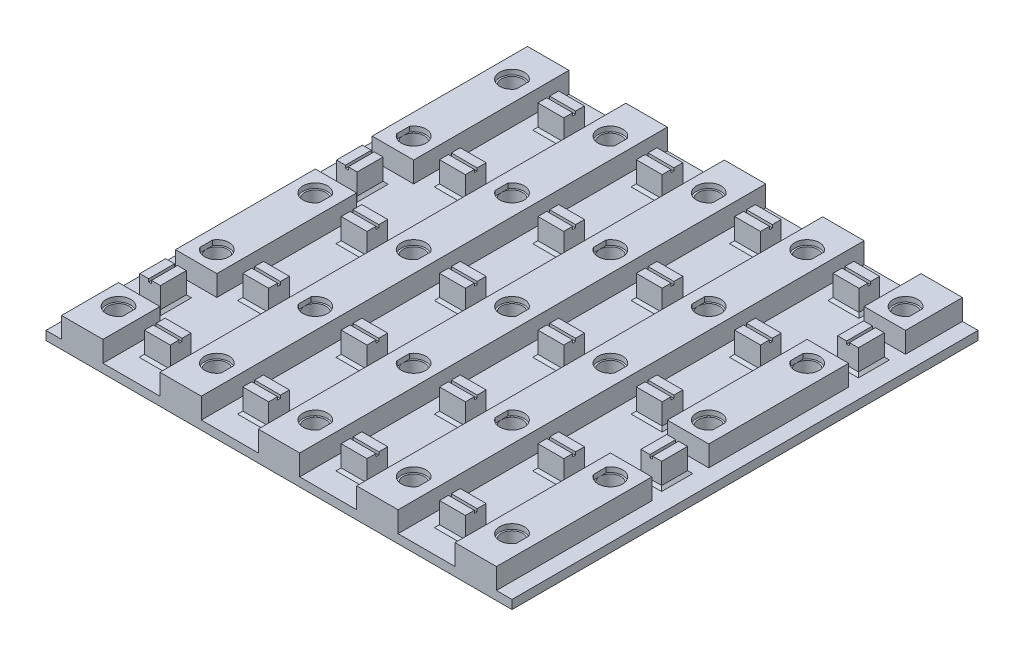
SolidWorks part; units mm, degrees
ref_plane "Front Plane" through (0, 0, 0) normal (0, 0, 1) x (1, 0, 0)
ref_plane "Top Plane" through (0, 0, 0) normal (0, 1, 0) x (1, 0, 0)
ref_plane "Right Plane" through (0, 0, 0) normal (1, 0, 0) x (0, 0, -1)
sketch "Sketch1" plane through (0, 0, 0) normal (0, 1, 0) x (1, 0, 0)
  line L1 (-110, -110) -> (110, -110)
  line L2 (-110, -110) -> (-110, 110)
  line L3 (-110, 110) -> (110, 110)
  line L4 (110, -110) -> (110, 110)
  line L5 (-110, -110) -> (110, 110) construction
  line L6 (-110, 110) -> (110, -110) construction
  point P0 (0, 0)
  dimension "D1" = 220
  dimension "D2" = 220
extrude "Boss-Extrude1" add sketch "Sketch1" along normal blind 11.4
sketch "Sketch2" plane through (0, 11.4, 0) normal (0, 1, 0) x (1, 0, 0)
  line L2 (-110, 110) -> (-110, -110) construction
  line L4 (-110, -110) -> (110, -110) construction
  circle A0 centre (-76, -76) radius 4.075
  circle A1 centre (-38, -76) radius 4.075
  circle A2 centre (0, -76) radius 4.075
  circle A3 centre (38, -76) radius 4.075
  circle A4 centre (76, -76) radius 4.075
  circle A5 centre (-76, -38) radius 4.075
  circle A6 centre (-38, -38) radius 4.075
  circle A7 centre (0, -38) radius 4.075
  circle A8 centre (38, -38) radius 4.075
  circle A9 centre (76, -38) radius 4.075
  circle A10 centre (-76, 0) radius 4.075
  circle A11 centre (-38, 0) radius 4.075
  circle A12 centre (0, 0) radius 4.075
  circle A13 centre (38, 0) radius 4.075
  circle A14 centre (76, 0) radius 4.075
  circle A15 centre (-76, 38) radius 4.075
  circle A16 centre (-38, 38) radius 4.075
  circle A17 centre (0, 38) radius 4.075
  circle A18 centre (38, 38) radius 4.075
  circle A19 centre (76, 38) radius 4.075
  circle A20 centre (-76, 76) radius 4.075
  circle A21 centre (-38, 76) radius 4.075
  circle A22 centre (0, 76) radius 4.075
  circle A23 centre (38, 76) radius 4.075
  circle A24 centre (76, 76) radius 4.075
  dimension "D1" = 8.15
  dimension "D5" = 38
  dimension "D7" = 38
  dimension "D2" = 34
  dimension "D3" = 34
  dimension "D4" = 5
  dimension "D6" = 5
extrude "Cut-Extrude1" cut sketch "Sketch2" against normal blind 11.5
sketch "Sketch10" plane through (0, 11.4, 0) normal (0, 1, 0) x (1, 0, 0)
  line L0 (-71.925, -78.4407) -> (-71.925, -73.5593)
  line L1 (-71.925, -2.4407) -> (-71.925, 2.4407)
  line L2 (-71.925, 73.5593) -> (-71.925, 78.4407)
  line L3 (-80.075, -35.5593) -> (-80.075, -40.4407)
  line L4 (-80.075, 40.4407) -> (-80.075, 35.5593)
  circle A0 centre (-76, -76) radius 4.075 construction
  arc A1 (-71.925, -73.5593) -> (-71.925, -78.4407) centre (-76, -76) ccw
  arc A2 (-71.925, 2.4407) -> (-71.925, -2.4407) centre (-76, 0) ccw
  arc A3 (-71.925, 78.4407) -> (-71.925, 73.5593) centre (-76, 76) ccw
  circle A4 centre (-76, 0) radius 4.075 construction
  circle A5 centre (-76, 76) radius 4.075 construction
  arc A6 (-80.075, -40.4407) -> (-80.075, -35.5593) centre (-76, -38) ccw
  arc A7 (-80.075, 35.5593) -> (-80.075, 40.4407) centre (-76, 38) ccw
  circle A8 centre (-76, 38) radius 4.075 construction
  circle A9 centre (-76, -38) radius 4.075 construction
  point P4 (-76, -76)
  point P7 (-76, -38)
  point P8 (-76, 0)
  point P9 (-76, 38)
  point P12 (-76, 76)
  point P17 (-76, 0)
  point P21 (-76, 76)
  point P24 (-76, 76)
  point P26 (-76, 38)
  point P33 (-76, -38)
  point P37 (-76, 38)
  dimension "D1" = 4.75
  dimension "D2" = 4.75
  dimension "D3" = 4.75
  dimension "D4" = 4.75
  dimension "D5" = 4.75
extrude "Cut-Extrude7" cut sketch "Sketch10" against normal blind 1.9
pattern_linear "LPattern2" count 5 spacing 38 along (1, 0, 0) of "Cut-Extrude7"
sketch "Sketch11" plane through (0, 11.4, 0) normal (0, 1, 0) x (1, 0, 0)
  line L0 (-84, 110) -> (-84, -110)
  line L10 (-110, -110) -> (110, -110) construction
  line L11 (-68, -110) -> (-68, 110)
  line L13 (-46, 110) -> (-46, -110)
  line L14 (-30, -110) -> (-30, 110)
  line L15 (-8, 110) -> (-8, -110)
  line L16 (8, -110) -> (8, 110)
  line L17 (30, 110) -> (30, -110)
  line L18 (46, -110) -> (46, 110)
  line L19 (68, 110) -> (68, -110)
  line L20 (84, -110) -> (84, 110)
  line L21 (-24, 80) -> (-14, 80)
  line L22 (-62, 80) -> (-52, 80)
  line L23 (-62, 80) -> (-62, 72)
  line L24 (-62, 72) -> (-52, 72)
  line L25 (-52, 80) -> (-52, 72)
  line L26 (-24, 80) -> (-24, 72)
  line L27 (-24, 72) -> (-14, 72)
  line L28 (-14, 80) -> (-14, 72)
  line L29 (14, 80) -> (24, 80)
  line L30 (14, 80) -> (14, 72)
  line L31 (14, 72) -> (24, 72)
  line L32 (24, 80) -> (24, 72)
  line L33 (52, 80) -> (62, 80)
  line L34 (52, 80) -> (52, 72)
  line L35 (52, 72) -> (62, 72)
  line L36 (62, 80) -> (62, 72)
  line L41 (-24, 42) -> (-14, 42)
  line L42 (-24, 42) -> (-24, 34)
  line L43 (-24, 34) -> (-14, 34)
  line L44 (-14, 42) -> (-14, 34)
  line L45 (14, 42) -> (24, 42)
  line L46 (14, 42) -> (14, 34)
  line L47 (14, 34) -> (24, 34)
  line L48 (24, 42) -> (24, 34)
  line L49 (52, 42) -> (62, 42)
  line L50 (52, 42) -> (52, 34)
  line L51 (52, 34) -> (62, 34)
  line L52 (62, 42) -> (62, 34)
  line L57 (-24, 4) -> (-14, 4)
  line L58 (-24, 4) -> (-24, -4)
  line L59 (-24, -4) -> (-14, -4)
  line L60 (-14, 4) -> (-14, -4)
  line L61 (14, 4) -> (24, 4)
  line L62 (14, 4) -> (14, -4)
  line L63 (14, -4) -> (24, -4)
  line L64 (24, 4) -> (24, -4)
  line L65 (52, 4) -> (62, 4)
  line L66 (52, 4) -> (52, -4)
  line L67 (52, -4) -> (62, -4)
  line L68 (62, 4) -> (62, -4)
  line L73 (-24, -34) -> (-14, -34)
  line L74 (-24, -34) -> (-24, -42)
  line L75 (-24, -42) -> (-14, -42)
  line L76 (-14, -34) -> (-14, -42)
  line L77 (14, -34) -> (24, -34)
  line L78 (14, -34) -> (14, -42)
  line L79 (14, -42) -> (24, -42)
  line L80 (24, -34) -> (24, -42)
  line L81 (52, -34) -> (62, -34)
  line L82 (52, -34) -> (52, -42)
  line L83 (52, -42) -> (62, -42)
  line L84 (62, -34) -> (62, -42)
  line L89 (-24, -72) -> (-14, -72)
  line L90 (-24, -72) -> (-24, -80)
  line L91 (-24, -80) -> (-14, -80)
  line L92 (-14, -72) -> (-14, -80)
  line L93 (14, -72) -> (24, -72)
  line L94 (14, -72) -> (14, -80)
  line L95 (14, -80) -> (24, -80)
  line L96 (24, -72) -> (24, -80)
  line L97 (52, -72) -> (62, -72)
  line L98 (52, -72) -> (52, -80)
  line L99 (52, -80) -> (62, -80)
  line L100 (62, -72) -> (62, -80)
  line L105 (-62, 42) -> (-52, 42)
  line L106 (-62, 42) -> (-62, 34)
  line L107 (-62, 34) -> (-52, 34)
  line L108 (-52, 42) -> (-52, 34)
  line L109 (-62, 4) -> (-52, 4)
  line L110 (-62, 4) -> (-62, -4)
  line L111 (-62, -4) -> (-52, -4)
  line L112 (-52, 4) -> (-52, -4)
  line L113 (-62, -34) -> (-52, -34)
  line L114 (-62, -34) -> (-62, -42)
  line L115 (-62, -42) -> (-52, -42)
  line L116 (-52, -34) -> (-52, -42)
  line L117 (-62, -72) -> (-52, -72)
  line L118 (-62, -72) -> (-62, -80)
  line L119 (-62, -80) -> (-52, -80)
  line L120 (-52, -72) -> (-52, -80)
  line L121 (0, -55) -> (0, 55) construction
  line L123 (-110, 110) -> (110, 110)
  line L124 (-110, 110) -> (-110, -110)
  line L125 (-110, -110) -> (110, -110)
  line L126 (110, 110) -> (110, -110)
  point P44 (-62, 76)
  point P45 (-76, 76)
  point P54 (-24, 76)
  point P59 (14, 76)
  point P64 (52, 76)
  point P74 (-24, 38)
  point P79 (14, 38)
  point P84 (52, 38)
  point P94 (-24, 0)
  point P99 (14, 0)
  point P104 (52, 0)
  point P114 (-24, -38)
  point P119 (14, -38)
  point P124 (52, -38)
  point P134 (-24, -76)
  point P139 (14, -76)
  point P144 (52, -76)
  point P154 (-62, 38)
  point P159 (-62, 0)
  point P164 (-62, -38)
  point P169 (-62, -76)
  point P171 (-38, 76)
  dimension "D2" = 8
  dimension "D4" = 8
  dimension "D5" = 14
  dimension "D6" = 14
  dimension "D7" = 8
  dimension "D10" = 14
  dimension "D11" = 30
  dimension "D12" = 14
  dimension "D13" = 8
  dimension "D3" = 5
  dimension "D8" = 4
  dimension "D9" = 5
extrude "Cut-Extrude8" cut sketch "Sketch11" against normal blind 8 contours L11 L125 L13 L123 L117 L120 L119 L118 L113 L116 L115 L114 L109 L112 L111 L110 L105 L108 L107 L106 L22 L25 L24 L23 | L14 L125 L15 L123 L89 L92 L91 L90 L73 L76 L75 L74 L57 L60 L59 L58 L41 L44 L43 L42 L21 L28 L27 L26 | L16 L125 L17 L123 L93 L96 L95 L94 L77 L80 L79 L78 L61 L64 L63 L62 L45 L48 L47 L46 L29 L32 L31 L30 | L18 L125 L19 L123 L97 L100 L99 L98 L81 L84 L83 L82 L65 L68 L67 L66 L49 L52 L51 L50 L33 L36 L35 L34 | L124 L125 L0 L123 | L126 L123 L20 L125
sketch "Sketch12" plane through (0, 11.4, 0) normal (0, 1, 0) x (1, 0, 0)
  line L0 (62, -72) -> (62, -80) construction
  line L1 (52, -72) -> (62, -72)
  line L2 (52, -72) -> (52, -75.45)
  line L3 (52, -75.45) -> (62, -75.45)
  line L4 (62, -72) -> (62, -75.45)
  line L5 (52, -72) -> (52, -80) construction
  line L6 (62, -80) -> (52, -80)
  line L7 (62, -80) -> (62, -76.55)
  line L8 (62, -76.55) -> (52, -76.55)
  line L9 (52, -80) -> (52, -76.55)
  line L10 (42.075, -76) -> (71.25, -76) construction
  line L11 (42.075, -78.4407) -> (42.075, -73.5593) construction
  line L12 (52, -76.55) -> (52, -75.45) construction
  arc A0 (80.075, -73.5593) -> (80.075, -78.4407) centre (76, -76) ccw construction
  point P21 (52, -76)
  dimension "D1" = 1.1
extrude "Boss-Extrude4" add sketch "Sketch12" along normal blind 1.1
pattern_linear "LPattern3" count 5 spacing 38 along (0, 0, -1) count 4 spacing 38 along (-1, 0, 0) of "Boss-Extrude4"
sketch "Sketch14" plane through (0, 11.4, 0) normal (0, 1, 0) x (1, 0, 0)
  line L0 (-81.8, 14) -> (-73.8, 14)
  line L5 (73.8, 52) -> (81.8, 52)
  line L18 (84, -110) -> (84, 110) construction
  line L19 (84, 46) -> (68, 46)
  line L20 (84, 46) -> (84, 68)
  line L21 (84, 68) -> (68, 68)
  line L22 (68, 46) -> (68, 68)
  line L23 (68, 110) -> (68, -110) construction
  line L24 (-84, 110) -> (-84, -110) construction
  line L25 (-84, 30) -> (-68, 30)
  line L26 (-84, 30) -> (-84, 8)
  line L27 (-84, 8) -> (-68, 8)
  line L28 (-68, 30) -> (-68, 8)
  line L29 (-68, -110) -> (-68, 110) construction
  line L30 (84, -110) -> (84, 110) construction
  line L31 (68, -8) -> (84, -8)
  line L32 (68, -8) -> (68, -30)
  line L33 (68, -30) -> (84, -30)
  line L34 (84, -8) -> (84, -30)
  line L35 (-68, -110) -> (-68, 110) construction
  line L36 (-84, -46) -> (-68, -46)
  line L37 (-84, -46) -> (-84, -68)
  line L38 (-84, -68) -> (-68, -68)
  line L39 (-68, -46) -> (-68, -68)
  line L40 (-6.875, 0) -> (6.875, 0) construction
  line L41 (73.8, 52) -> (73.8, 62)
  line L42 (73.8, 62) -> (81.8, 62)
  line L43 (81.8, 52) -> (81.8, 62)
  line L44 (73.8, 52) -> (81.8, 62) construction
  line L45 (73.8, 62) -> (81.8, 52) construction
  line L46 (-81.8, 14) -> (-81.8, 24)
  line L47 (-81.8, 24) -> (-73.8, 24)
  line L48 (-73.8, 14) -> (-73.8, 24)
  line L49 (-81.8, 14) -> (-73.8, 24) construction
  line L50 (-81.8, 24) -> (-73.8, 14) construction
  line L51 (-81.8, -62) -> (-73.8, -62)
  line L52 (-81.8, -62) -> (-81.8, -52)
  line L53 (-81.8, -52) -> (-73.8, -52)
  line L54 (-73.8, -62) -> (-73.8, -52)
  line L55 (-81.8, -62) -> (-73.8, -52) construction
  line L56 (-81.8, -52) -> (-73.8, -62) construction
  line L57 (73.8, -24) -> (81.8, -24)
  line L58 (73.8, -24) -> (73.8, -14)
  line L59 (73.8, -14) -> (81.8, -14)
  line L60 (81.8, -24) -> (81.8, -14)
  line L61 (73.8, -24) -> (81.8, -14) construction
  line L62 (73.8, -14) -> (81.8, -24) construction
  point P10 (77.8, 57)
  point P30 (76, 76)
  point P31 (76, 38)
  point P32 (-76, 38)
  point P33 (-76, 0)
  point P34 (76, 0)
  point P35 (76, -38)
  point P38 (-76, -38)
  point P39 (-76, -76)
  point P43 (-84, -57)
  point P44 (84, 57)
  point P45 (77.8, -19)
  point P47 (-77.8, 19)
  point P60 (-84, 19)
  point P63 (-77.8, -57)
  dimension "D1" = 8
  dimension "D2" = 8
  dimension "D4" = 8
  dimension "D3" = 8
  dimension "D5" = 8
  dimension "D6" = 8
  dimension "D7" = 8
  dimension "D8" = 8
  dimension "D9" = 10
  dimension "D10" = 8
  dimension "D11" = 8
  dimension "D12" = 10
  dimension "D14" = 1.8
  dimension "D15" = 1.8
  dimension "D13" = 2
extrude "Cut-Extrude9" cut sketch "Sketch14" against normal up to surface (8 mm away) up to face at (-97, 3.4, 0)
sketch "Sketch16" plane through (0, 11.4, 0) normal (0, 1, 0) x (1, 0, 0)
  line L0 (81.8, 62) -> (73.8, 62) construction
  line L1 (73.8, 62) -> (77.25, 62)
  line L2 (73.8, 62) -> (73.8, 52)
  line L3 (73.8, 52) -> (77.25, 52)
  line L4 (77.25, 62) -> (77.25, 52)
  line L5 (73.8, 62) -> (73.8, 52) construction
  line L6 (73.8, 52) -> (81.8, 52) construction
  line L7 (73.8, 62) -> (81.8, 62) construction
  line L8 (81.8, 52) -> (78.35, 52)
  line L9 (81.8, 52) -> (81.8, 62)
  line L10 (81.8, 62) -> (78.35, 62)
  line L11 (78.35, 52) -> (78.35, 62)
  line L12 (77.25, 62) -> (78.35, 62) construction
  line L13 (-81.8, 24) -> (-78.35, 24)
  line L14 (-81.8, 24) -> (-81.8, 14)
  line L15 (-81.8, 14) -> (-78.35, 14)
  line L16 (-78.35, 24) -> (-78.35, 14)
  line L17 (-73.8, 14) -> (-77.25, 14)
  line L18 (-73.8, 14) -> (-73.8, 24)
  line L19 (-73.8, 24) -> (-77.25, 24)
  line L20 (-77.25, 14) -> (-77.25, 24)
  line L21 (-78.35, 24) -> (-77.25, 24) construction
  line L22 (-73.8, 24) -> (-81.8, 24) construction
  line L23 (-81.8, 24) -> (-81.8, 14) construction
  line L24 (73.8, -14) -> (77.25, -14)
  line L25 (73.8, -14) -> (73.8, -24)
  line L26 (73.8, -24) -> (77.25, -24)
  line L27 (77.25, -14) -> (77.25, -24)
  line L28 (81.8, -24) -> (78.35, -24)
  line L29 (81.8, -24) -> (81.8, -14)
  line L30 (81.8, -14) -> (78.35, -14)
  line L31 (78.35, -24) -> (78.35, -14)
  line L32 (-81.8, -52) -> (-78.35, -52)
  line L33 (-81.8, -52) -> (-81.8, -62)
  line L34 (-81.8, -62) -> (-78.35, -62)
  line L35 (-78.35, -52) -> (-78.35, -62)
  line L36 (-73.8, -62) -> (-77.25, -62)
  line L37 (-73.8, -62) -> (-73.8, -52)
  line L38 (-73.8, -52) -> (-77.25, -52)
  line L39 (-77.25, -62) -> (-77.25, -52)
  line L40 (77.25, -14) -> (78.35, -14) construction
  line L41 (-78.35, -52) -> (-77.25, -52) construction
  line L42 (-81.8, -52) -> (-73.8, -52) construction
  point P18 (77.8, 62)
  point P29 (-77.8, 24)
  point P43 (77.8, -14)
  point P52 (-77.8, -52)
  dimension "D1" = 1.1
  dimension "D2" = 1.1
  dimension "D3" = 2
extrude "Boss-Extrude5" add sketch "Sketch16" along normal up to surface (1.1 mm away) up to face at (-57, 12.5, 40.275)
chamfer "Chamfer3" distance 1 angle 45 96 edges at (73.8, 3.4, -57) (77.8, 3.4, -52) (81.8, 3.4, -57) (77.8, 3.4, -62) (73.8, 3.4, 19) (77.8, 3.4, 24) (81.8, 3.4, 19) (77.8, 3.4, 14) (52, 3.4, -76) (57, 3.4, -72) (62, 3.4, -76) (57, 3.4, -80) (52, 3.4, 76) (57, 3.4, 80) (62, 3.4, 76) (57, 3.4, 72) (52, 3.4, 38) (57, 3.4, 42) (62, 3.4, 38) (57, 3.4, 34) (52, 3.4, 0) (57, 3.4, 4) (62, 3.4, 0) (57, 3.4, -4) (52, 3.4, -38) (57, 3.4, -34) (62, 3.4, -38) (57, 3.4, -42) (14, 3.4, -76) (19, 3.4, -72) (24, 3.4, -76) (19, 3.4, -80) (14, 3.4, -38) (19, 3.4, -34) (24, 3.4, -38) (19, 3.4, -42) (14, 3.4, 0) (19, 3.4, 4) (24, 3.4, 0) (19, 3.4, -4) (14, 3.4, 38) (19, 3.4, 42) (24, 3.4, 38) (19, 3.4, 34) (14, 3.4, 76) (19, 3.4, 80) (24, 3.4, 76) (19, 3.4, 72) (-81.8, 3.4, -19) (-77.8, 3.4, -14) (-73.8, 3.4, -19) (-77.8, 3.4, -24) (-81.8, 3.4, 57) (-77.8, 3.4, 62) (-73.8, 3.4, 57) (-77.8, 3.4, 52) (-62, 3.4, 76) (-57, 3.4, 80) (-52, 3.4, 76) (-57, 3.4, 72) (-62, 3.4, 38) (-57, 3.4, 42) (-52, 3.4, 38) (-57, 3.4, 34) (-62, 3.4, 0) (-57, 3.4, 4) (-52, 3.4, 0) (-57, 3.4, -4) (-62, 3.4, -38) (-57, 3.4, -34) (-52, 3.4, -38) (-57, 3.4, -42) (-62, 3.4, -76) (-57, 3.4, -72) (-52, 3.4, -76) (-57, 3.4, -80) (-24, 3.4, -38) (-19, 3.4, -34) (-14, 3.4, -38) (-19, 3.4, -42) (-24, 3.4, -76) (-19, 3.4, -72) (-14, 3.4, -76) (-19, 3.4, -80) (-24, 3.4, 76) (-19, 3.4, 80) (-14, 3.4, 76) (-19, 3.4, 72) (-24, 3.4, 38) (-19, 3.4, 42) (-14, 3.4, 38) (-19, 3.4, 34) (-24, 3.4, 0) (-19, 3.4, 4) (-14, 3.4, 0) (-19, 3.4, -4)
sketch "Sketch17" plane through (0, 3.4, 0) normal (0, 1, 0) x (1, 0, 0)
  line L0 (-110, -110) -> (-84, -110) construction
  line L1 (-110, 110) -> (-90, 110)
  line L2 (-110, 110) -> (-110, -110)
  line L3 (-110, -110) -> (-90, -110)
  line L4 (-90, 110) -> (-90, -110)
  line L5 (84, 110) -> (110, 110) construction
  line L6 (110, -110) -> (90, -110)
  line L7 (110, -110) -> (110, 110)
  line L8 (110, 110) -> (90, 110)
  line L9 (90, -110) -> (90, 110)
  dimension "D1" = 20
  dimension "D2" = 20
extrude "Cut-Extrude10" cut sketch "Sketch17" against normal through all
sketch "Sketch18" plane through (0, 11.4, 0) normal (0, 1, 0) x (1, 0, 0)
  line L0 (90, 110) -> (90, -110) construction
  line L1 (-90, 110) -> (90, 110)
  line L2 (-90, 110) -> (-90, 90)
  line L3 (-90, 90) -> (90, 90)
  line L4 (90, 110) -> (90, 90)
  line L5 (-90, -110) -> (-90, 110) construction
  line L6 (90, -110) -> (-90, -110)
  line L7 (90, -110) -> (90, -90)
  line L8 (90, -90) -> (-90, -90)
  line L9 (-90, -110) -> (-90, -90)
  dimension "D1" = 20
  dimension "D2" = 20
extrude "Cut-Extrude11" cut sketch "Sketch18" against normal through all
